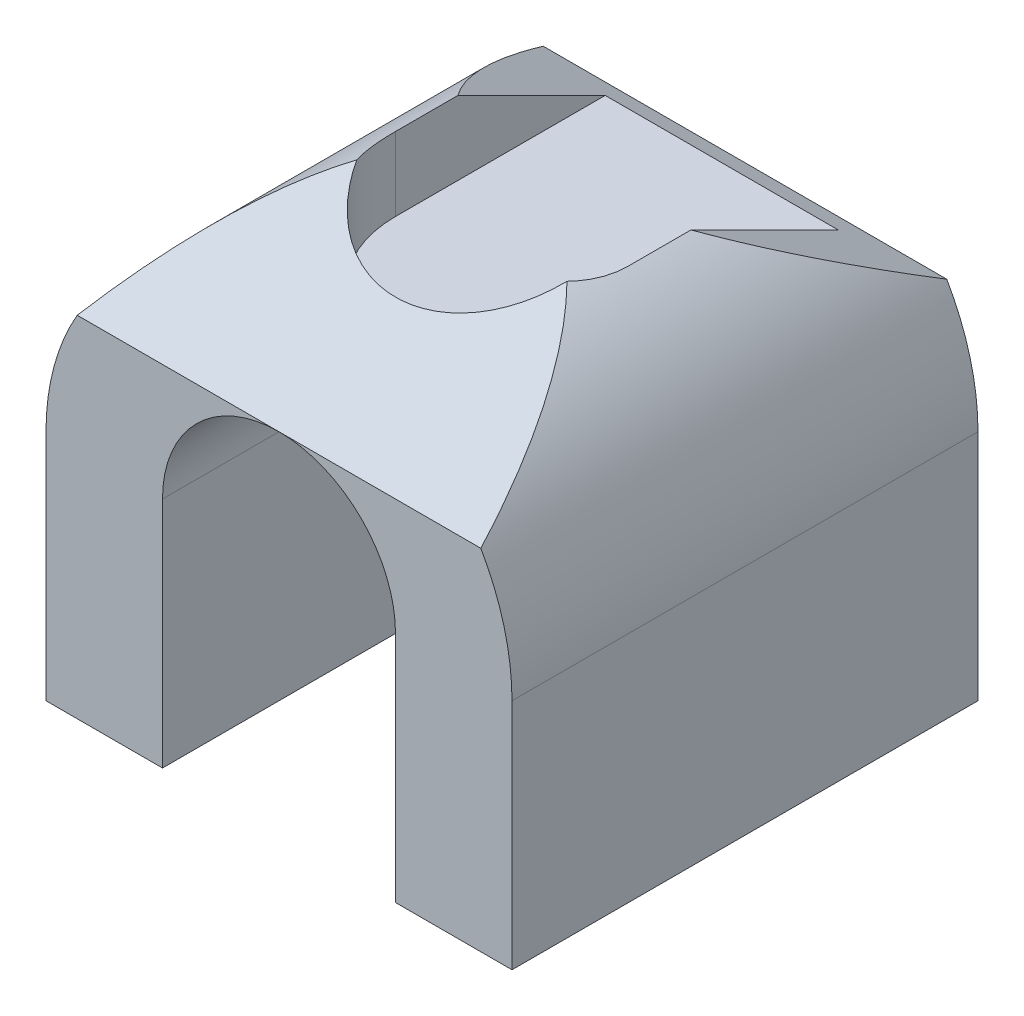
SolidWorks part; units mm, degrees
ref_plane "Front" through (0, 0, 0) normal (0, 0, 1) x (1, 0, 0)
ref_plane "Top" through (0, 0, 0) normal (0, 1, 0) x (1, 0, 0)
ref_plane "Right" through (0, 0, 0) normal (1, 0, 0) x (0, 0, -1)
sketch "Sketch1" plane through (0, 0, 0) normal (0, 1, 0) x (1, 0, 0)
  line L1 (-2, -2) -> (2, -2)
  line L2 (-2, -2) -> (-2, 2)
  line L3 (-2, 2) -> (2, 2)
  line L4 (2, -2) -> (2, 2)
  line L5 (-2, -2) -> (2, 2) construction
  line L6 (-2, 2) -> (2, -2) construction
  point P0 (0, 0)
  dimension "D1" = 4
  dimension "D2" = 4
extrude "Boss-Extrude1" add sketch "Sketch1" along normal blind 4
sketch "Sketch4" plane through (-2, 0, 0) normal (-1, 0, 0) x (0, 0, 1)
  line L0 (-2, 3) -> (0, 4)
  line L1 (0, 4) -> (2, 3)
  line L4 (-2, 0) -> (2, 0)
  line L5 (2, 0) -> (2, 4)
  line L6 (2, 4) -> (-2, 4)
  line L7 (-2, 4) -> (-2, 0)
  line L8 (-2, 0) -> (2, 0)
  line L9 (2, 0) -> (2, 4)
  line L10 (2, 4) -> (-2, 4)
  line L11 (-2, 4) -> (-2, 0)
  line M8 (2, 0) -> (2, 4)
  line M9 (2, 4) -> (-2, 4)
  line M10 (-2, 4) -> (-2, 0)
  dimension "D2" = 1
  dimension "D3" = 1
  dimension "D1" = 0
extrude "Cut-Extrude1" cut sketch "Sketch4" against normal blind 10 contours L0 M10 M9 | L1 M9 M8 region at (-2, 3.6667, -1.3333) region at (-2, 3.6667, 1.3333)
sketch "Sketch5" plane through (0, 0, 2) normal (0, 0, 1) x (1, 0, 0)
  line L0 (2, 4) -> (-2, 4) construction
  line L1 (-2, 4) -> (-2, 3) construction
  line L2 (2, 3) -> (2, 4) construction
  line L3 (2, 0) -> (2, 3) construction
  line L4 (-2, 3) -> (-2, 0) construction
  line L5 (-2, 0) -> (2, 0) construction
  line L6 (2, 4) -> (-2, 4)
  line L7 (-2, 4) -> (-2, 3)
  line L8 (2, 3) -> (2, 4)
  line L9 (2, 0) -> (2, 3)
  line L10 (-2, 3) -> (-2, 0)
  line L11 (-2, 0) -> (2, 0)
  line L12 (0, 0) -> (0, 2) construction
  line L13 (-1, 0) -> (-1, 2)
  line L14 (1, 0) -> (1, 2)
  arc A0 (-2, 2) -> (2, 2) centre (0, 2) cw
  arc A1 (-1, 0) -> (1, 0) centre (0, 0) ccw
  arc A2 (1, 2) -> (-1, 2) centre (0, 2) ccw
  point P10 (0, 1)
  line M2 (2, 3) -> (-2, 3)
  line M3 (-2, 3) -> (-2, 0)
  line M4 (-2, 0) -> (2, 0)
  dimension "D3" = 1
  dimension "D1" = 2
  dimension "D2" = 2
extrude "Cut-Extrude2" cut sketch "Sketch5" against normal blind 10 contours L14 A2 L13 L11 M4 | A0 L6 L7 M2 | L6 A0 L8 M2 | A0 L9 M2 | A0 M3 M2 region at (1.512, 3.6432, 2) region at (-1.512, 3.6432, 2) region at (1.9206, 2.7535, 2) region at (-1.9206, 2.7535, 2) region at (0, 1.4016, 2)
ref_plane "Plane1" through (0, 4, 0) normal (0, 1, 0) x (1, 0, 0)
sketch "Sketch6" plane through (0, 4, 0) normal (0, 1, 0) x (1, 0, 0)
  line L0 (0, 0) -> (0, 2) construction
  line L1 (-1, 0) -> (-1, 2)
  line L2 (1, 0) -> (1, 2)
  arc A0 (-1, 0) -> (1, 0) centre (0, 0) ccw
  arc A1 (1, 2) -> (-1, 2) centre (0, 2) ccw
  point P4 (0, 1)
  dimension "D1" = 1
extrude "Cut-Extrude5" cut sketch "Sketch6" against normal blind 0.9
